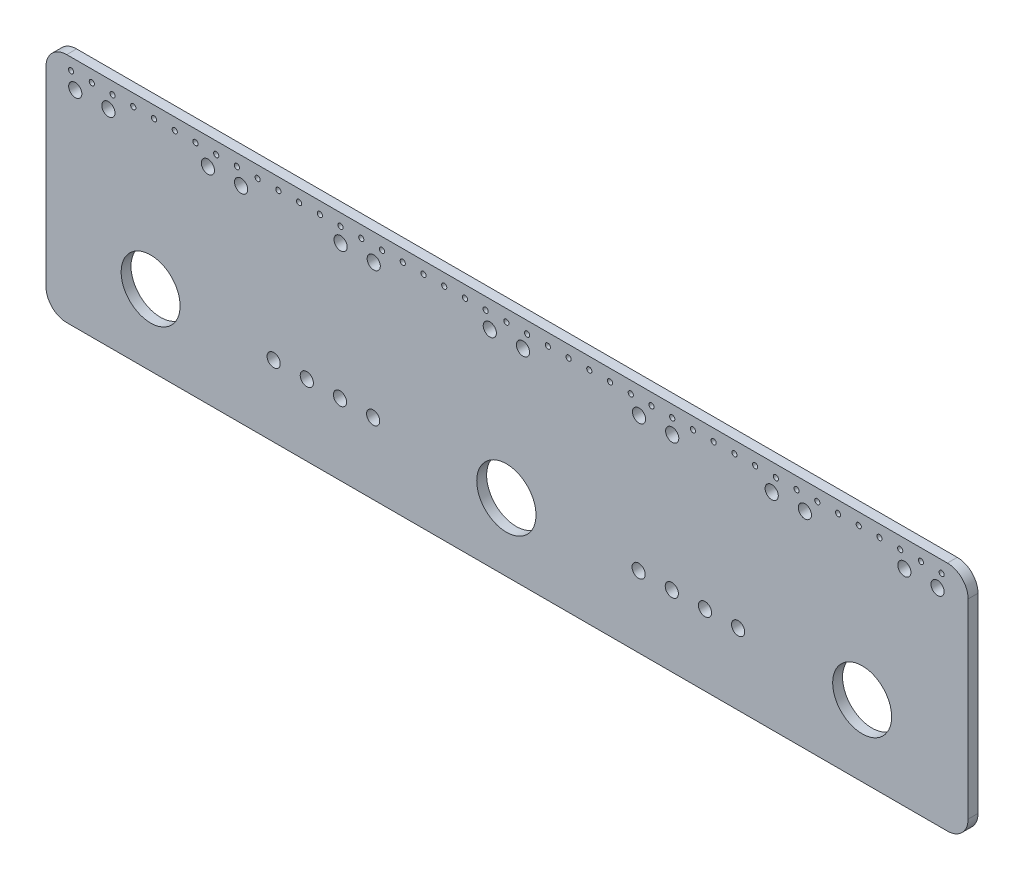
SolidWorks part; units mm, degrees
ref_plane "Front" through (0, 0, 0) normal (0, 0, 1) x (1, 0, 0)
ref_plane "Top" through (0, 0, 0) normal (0, 1, 0) x (1, 0, 0)
ref_plane "Right" through (0, 0, 0) normal (1, 0, 0) x (0, 0, -1)
sketch "Sketch1" plane through (0, 0, 0) normal (0, 0, 1) x (1, 0, 0)
  line L0 (-577.3643, 112.6847) -> (-152.4843, 112.6847)
  line L1 (-587.3643, 102.6847) -> (-587.3643, 10.6847)
  line L2 (-577.3643, 0.6847) -> (-152.4843, 0.6847)
  line L3 (-142.4843, 102.6847) -> (-142.4843, 10.6847)
  circle A328 centre (-301.253, 99.9347) radius 3.18
  circle A329 centre (-285.253, 99.9347) radius 3.18
  circle A330 centre (-237.253, 99.9347) radius 3.18
  circle A331 centre (-221.253, 99.9347) radius 3.18
  circle A332 centre (-173.253, 99.9347) radius 3.18
  circle A333 centre (-157.253, 99.9347) radius 3.18
  circle A334 centre (-445.253, 99.9347) radius 3.18
  circle A335 centre (-429.253, 99.9347) radius 3.18
  circle A336 centre (-509.253, 99.9347) radius 3.18
  circle A337 centre (-493.253, 99.9347) radius 3.18
  circle A338 centre (-573.253, 99.9347) radius 3.18
  circle A339 centre (-557.253, 99.9347) radius 3.18
  circle A340 centre (-357.253, 99.9347) radius 3.18
  circle A341 centre (-373.253, 99.9347) radius 3.18
  circle A397 centre (-536.893, 34.9847) radius 14.225
  circle A398 centre (-193.613, 34.9847) radius 14.225
  circle A399 centre (-365.253, 33.4847) radius 14.3
  arc A400 (-152.4843, 0.6847) -> (-142.4843, 10.6847) centre (-152.4843, 10.6847) ccw
  arc A401 (-577.3643, 0.6847) -> (-587.3643, 10.6847) centre (-577.3643, 10.6847) cw
  arc A402 (-577.3643, 112.6847) -> (-587.3643, 102.6847) centre (-577.3643, 102.6847) ccw
  arc A403 (-152.4843, 112.6847) -> (-142.4843, 102.6847) centre (-152.4843, 102.6847) cw
  circle A435 centre (-477.534, 34.9847) radius 3.18
  circle A437 centre (-461.534, 34.9847) radius 3.18
  circle A439 centre (-445.534, 34.9847) radius 3.18
  circle A441 centre (-429.534, 34.9847) radius 3.18
  circle A443 centre (-301.443, 34.9847) radius 3.18
  circle A444 centre (-285.443, 34.9847) radius 3.18
  circle A445 centre (-269.443, 34.9847) radius 3.18
  circle A446 centre (-253.443, 34.9847) radius 3.18
  circle A473 centre (-365.253, 106.9847) radius 1.25
  circle A483 centre (-355.253, 106.9847) radius 1.25
  circle A484 centre (-345.253, 106.9847) radius 1.25
  circle A485 centre (-335.253, 106.9847) radius 1.25
  circle A486 centre (-325.253, 106.9847) radius 1.25
  circle A487 centre (-315.253, 106.9847) radius 1.25
  circle A488 centre (-305.253, 106.9847) radius 1.25
  circle A489 centre (-295.253, 106.9847) radius 1.25
  circle A490 centre (-285.253, 106.9847) radius 1.25
  circle A491 centre (-275.253, 106.9847) radius 1.25
  circle A492 centre (-265.253, 106.9847) radius 1.25
  circle A493 centre (-255.253, 106.9847) radius 1.25
  circle A494 centre (-245.253, 106.9847) radius 1.25
  circle A495 centre (-235.253, 106.9847) radius 1.25
  circle A496 centre (-225.253, 106.9847) radius 1.25
  circle A497 centre (-215.253, 106.9847) radius 1.25
  circle A498 centre (-205.253, 106.9847) radius 1.25
  circle A499 centre (-195.253, 106.9847) radius 1.25
  circle A500 centre (-185.253, 106.9847) radius 1.25
  circle A501 centre (-175.253, 106.9847) radius 1.25
  circle A502 centre (-165.253, 106.9847) radius 1.25
  circle A503 centre (-155.253, 106.9847) radius 1.25
  circle A504 centre (-375.253, 106.9847) radius 1.25
  circle A505 centre (-385.253, 106.9847) radius 1.25
  circle A506 centre (-395.253, 106.9847) radius 1.25
  circle A507 centre (-405.253, 106.9847) radius 1.25
  circle A508 centre (-415.253, 106.9847) radius 1.25
  circle A509 centre (-425.253, 106.9847) radius 1.25
  circle A510 centre (-435.253, 106.9847) radius 1.25
  circle A511 centre (-445.253, 106.9847) radius 1.25
  circle A512 centre (-455.253, 106.9847) radius 1.25
  circle A513 centre (-465.253, 106.9847) radius 1.25
  circle A514 centre (-475.253, 106.9847) radius 1.25
  circle A515 centre (-485.253, 106.9847) radius 1.25
  circle A516 centre (-495.253, 106.9847) radius 1.25
  circle A517 centre (-505.253, 106.9847) radius 1.25
  circle A518 centre (-515.253, 106.9847) radius 1.25
  circle A519 centre (-525.253, 106.9847) radius 1.25
  circle A520 centre (-535.253, 106.9847) radius 1.25
  circle A521 centre (-545.253, 106.9847) radius 1.25
  circle A522 centre (-555.253, 106.9847) radius 1.25
  circle A523 centre (-565.253, 106.9847) radius 1.25
  circle A524 centre (-575.253, 106.9847) radius 1.25
  point P51 (-142.813, 112.6847)
extrude "Boss-Extrude1" add sketch "Sketch1" along normal blind 4.7625
move or copy body "Body-Move/Copy1" [suppressed] bodies to move or copy 107
